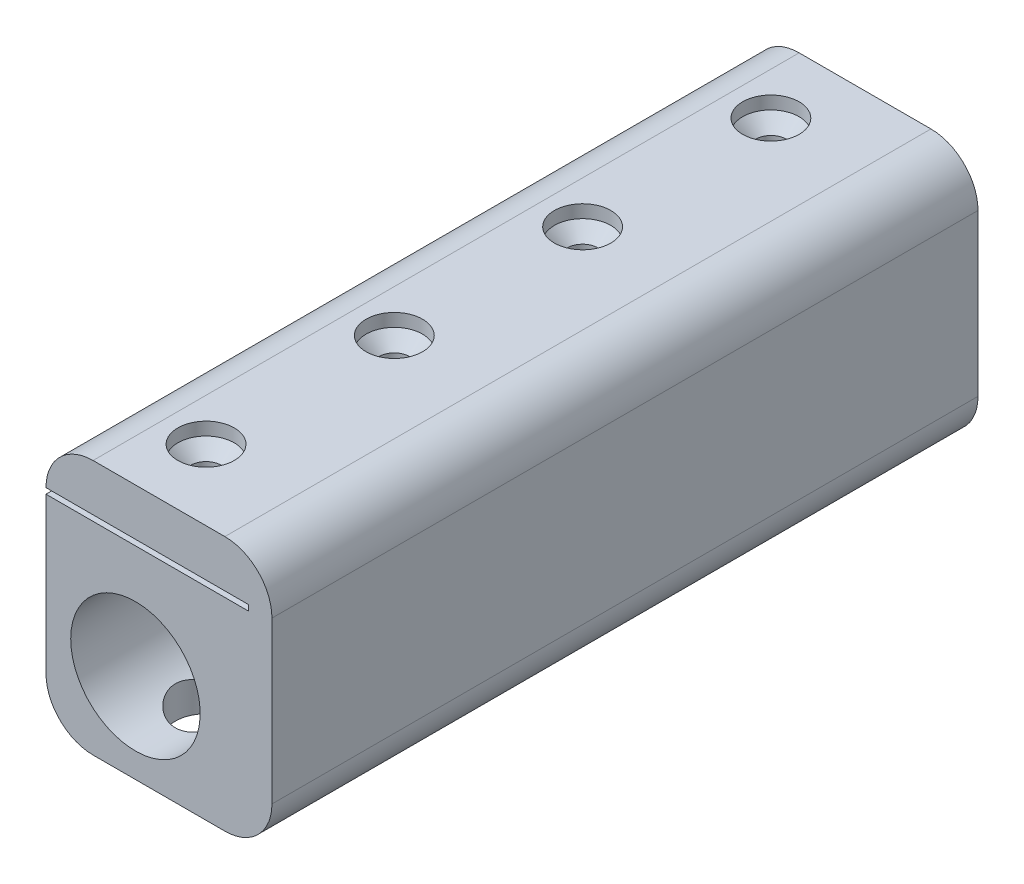
SolidWorks part; units mm, degrees
ref_plane "Front Plane" through (0, 0, 0) normal (0, 0, 1) x (1, 0, 0)
ref_plane "Top Plane" through (0, 0, 0) normal (0, 1, 0) x (1, 0, 0)
ref_plane "Right Plane" through (0, 0, 0) normal (1, 0, 0) x (0, 0, -1)
sketch "Sketch1" plane through (0, 0, 0) normal (0, 0, 1) x (1, 0, 0)
  line L1 (-24, -24) -> (24, -24)
  line L2 (-24, -24) -> (-24, 24)
  line L3 (-24, 24) -> (24, 24)
  line L4 (24, -24) -> (24, 24)
  line L5 (-24, -24) -> (24, 24) construction
  line L6 (-24, 24) -> (24, -24) construction
  line L7 (24, -24) -> (29, -24)
  line L8 (24, -24) -> (24, 35.2)
  line L9 (24, 35.2) -> (29, 35.2)
  line L10 (29, -24) -> (29, 35.2)
  line L11 (24, 35.2) -> (-24, 35.2)
  line L12 (24, 35.2) -> (24, 25.2)
  line L13 (24, 25.2) -> (-24, 25.2)
  line L14 (-24, 35.2) -> (-24, 25.2)
  circle A0 centre (0, 0) radius 13.75
  dimension "D1" = 27.5
  dimension "D2" = 1.2
  dimension "D3" = 48
  dimension "D4" = 48
  dimension "D5" = 5
  dimension "D6" = 10
extrude "Boss-Extrude1" add sketch "Sketch1" along normal blind 230 contours L1 L4 L3 L2 A0 | L11 L14 L13 L8 | L7 L10 L9 L8 L4 region at (-23.3212, 0, 0) region at (26.5, 5.6, 0) region at (0, 30.2, 0)
sketch "Sketch3" plane through (0, 35.2, 0) normal (0, 1, 0) x (1, 0, 0)
  line L0 (0, 0) -> (0, -230) construction
  line L1 (-24, -230) -> (29, -230) construction
  circle A0 centre (0, -15) radius 6
  circle A1 centre (0, -55) radius 6
  circle A2 centre (0, -95) radius 6
  circle A3 centre (0, -135) radius 6
  circle A4 centre (0, -175) radius 6
  circle A5 centre (0, -215) radius 6
  dimension "D1" = 12
  dimension "D2" = 15
  dimension "D4" = 15
  dimension "D3" = 6
extrude "Cut-Extrude1" cut sketch "Sketch3" against normal blind 0.5
sketch "Sketch4" plane through (0, 35.2, 0) normal (0, 1, 0) x (1, 0, 0)
  line L0 (0, 0) -> (0, -230) construction
  line L1 (-24, -230) -> (29, -230) construction
  circle A0 centre (0, -15) radius 3.25
  circle A1 centre (0, -55) radius 3.25
  circle A2 centre (0, -95) radius 3.25
  circle A3 centre (0, -135) radius 3.25
  circle A4 centre (0, -175) radius 3.25
  circle A5 centre (0, -215) radius 3.25
  dimension "D1" = 6.5
  dimension "D2" = 6
extrude "Cut-Extrude2" cut sketch "Sketch4" against normal through all
sketch "Sketch5" plane through (0, -24, 0) normal (0, -1, 0) x (1, 0, 0)
  line L0 (0, 230) -> (0, 0) construction
  line L1 (-24, 230) -> (29, 230) construction
  circle A0 centre (0, 215) radius 6.5
  circle A1 centre (0, 175) radius 6.5
  circle A2 centre (0, 135) radius 6.5
  circle A3 centre (0, 95) radius 6.5
  circle A4 centre (0, 55) radius 6.5
  circle A5 centre (0, 15) radius 6.5
  dimension "D1" = 13
  dimension "D2" = 6
extrude "Cut-Extrude3" cut sketch "Sketch5" against normal up to next
sketch "Sketch7" plane through (0, 24, 0) normal (0, 1, 0) x (1, 0, 0)
  line L0 (0, 0) -> (0, -230) construction
  line L1 (0, -8.5337) -> (-5.6, -11.7668)
  line L2 (-5.6, -11.7668) -> (-5.6, -18.2332)
  line L3 (-5.6, -18.2332) -> (0, -21.4663)
  line L4 (0, -21.4663) -> (5.6, -18.2332)
  line L5 (5.6, -18.2332) -> (5.6, -11.7668)
  line L6 (5.6, -11.7668) -> (0, -8.5337)
  line L7 (-24, -230) -> (29, -230) construction
  line L8 (0, -48.5337) -> (-5.6, -51.7668)
  line L9 (-5.6, -51.7668) -> (-5.6, -58.2332)
  line L10 (-5.6, -58.2332) -> (0, -61.4663)
  line L11 (0, -61.4663) -> (5.6, -58.2332)
  line L12 (5.6, -58.2332) -> (5.6, -51.7668)
  line L13 (5.6, -51.7668) -> (0, -48.5337)
  line L14 (0, -88.5337) -> (-5.6, -91.7668)
  line L15 (-5.6, -91.7668) -> (-5.6, -98.2332)
  line L16 (-5.6, -98.2332) -> (0, -101.4663)
  line L17 (0, -101.4663) -> (5.6, -98.2332)
  line L18 (5.6, -98.2332) -> (5.6, -91.7668)
  line L19 (5.6, -91.7668) -> (0, -88.5337)
  line L20 (0, -128.5337) -> (-5.6, -131.7668)
  line L21 (-5.6, -131.7668) -> (-5.6, -138.2332)
  line L22 (-5.6, -138.2332) -> (0, -141.4663)
  line L23 (0, -141.4663) -> (5.6, -138.2332)
  line L24 (5.6, -138.2332) -> (5.6, -131.7668)
  line L25 (5.6, -131.7668) -> (0, -128.5337)
  line L26 (0, -168.5337) -> (-5.6, -171.7668)
  line L27 (-5.6, -171.7668) -> (-5.6, -178.2332)
  line L28 (-5.6, -178.2332) -> (0, -181.4663)
  line L29 (0, -181.4663) -> (5.6, -178.2332)
  line L30 (5.6, -178.2332) -> (5.6, -171.7668)
  line L31 (5.6, -171.7668) -> (0, -168.5337)
  line L32 (0, -208.5337) -> (-5.6, -211.7668)
  line L33 (-5.6, -211.7668) -> (-5.6, -218.2332)
  line L34 (-5.6, -218.2332) -> (0, -221.4663)
  line L35 (0, -221.4663) -> (5.6, -218.2332)
  line L36 (5.6, -218.2332) -> (5.6, -211.7668)
  line L37 (5.6, -211.7668) -> (0, -208.5337)
  circle A0 centre (0, -15) radius 5.6 construction
  dimension "D1" = 11.2
  dimension "D2" = 6
extrude "Cut-Extrude4" cut sketch "Sketch7" against normal up to next from offset 5 offset against normal yes
chamfer "Chamfer1" distance 5 angle 45 6 edges at (0, 34.7, 218.25) (0, 34.7, 178.25) (0, 34.7, 138.25) (0, 34.7, 98.25) (0, 34.7, 58.25) (0, 34.7, 18.25)
sketch "Sketch12" plane through (0, 35.2, 0) normal (0, 1, 0) x (1, 0, 0)
  line L0 (29, -230) -> (29, 0) construction
  line L1 (-24, -230) -> (29, -230)
  line L2 (-24, -230) -> (-24, -150)
  line L3 (-24, -150) -> (29, -150)
  line L4 (29, -230) -> (29, -150)
  dimension "D1" = 80
extrude "Cut-Extrude5" cut sketch "Sketch12" against normal through all
sketch "Sketch14" plane through (0, 0, 0) normal (0, 0, -1) x (-1, 0, 0)
  line L1 (-29, -24) -> (24, -24)
  line L2 (-29, -24) -> (-29, -19)
  line L3 (-29, -19) -> (24, -19)
  line L4 (24, -24) -> (24, -19)
  line L5 (24, 35.2) -> (19, 35.2)
  line L6 (24, 35.2) -> (24, -19)
  line L7 (24, -19) -> (19, -19)
  line L8 (19, 35.2) -> (19, -19)
  line M5 (-29, -24) -> (24, -24)
  line M6 (24, -24) -> (24, 24)
  line M7 (24, 24) -> (-24, 24)
  line M9 (-24, 25.2) -> (24, 25.2)
  line M10 (24, 25.2) -> (24, 35.2)
  line M11 (24, 35.2) -> (-29, 35.2)
  line M12 (-29, 35.2) -> (-29, -24)
  dimension "D1" = 5
  dimension "D2" = 5
extrude "Cut-Extrude6" cut sketch "Sketch14" against normal through all contours L8 L3 M7 M6 | L8 M11 M9 M10 | L3 M12 M5 M6 region at (2.5, -21.5, 0) region at (-21.5, 2.5, 0) region at (-21.5, 30.2, 0)
fillet "Fillet1" radius 10 4 edges at (29, -19, 75) (-19, -19, 75) (29, 35.2, 75) (-19, 35.2, 75)
